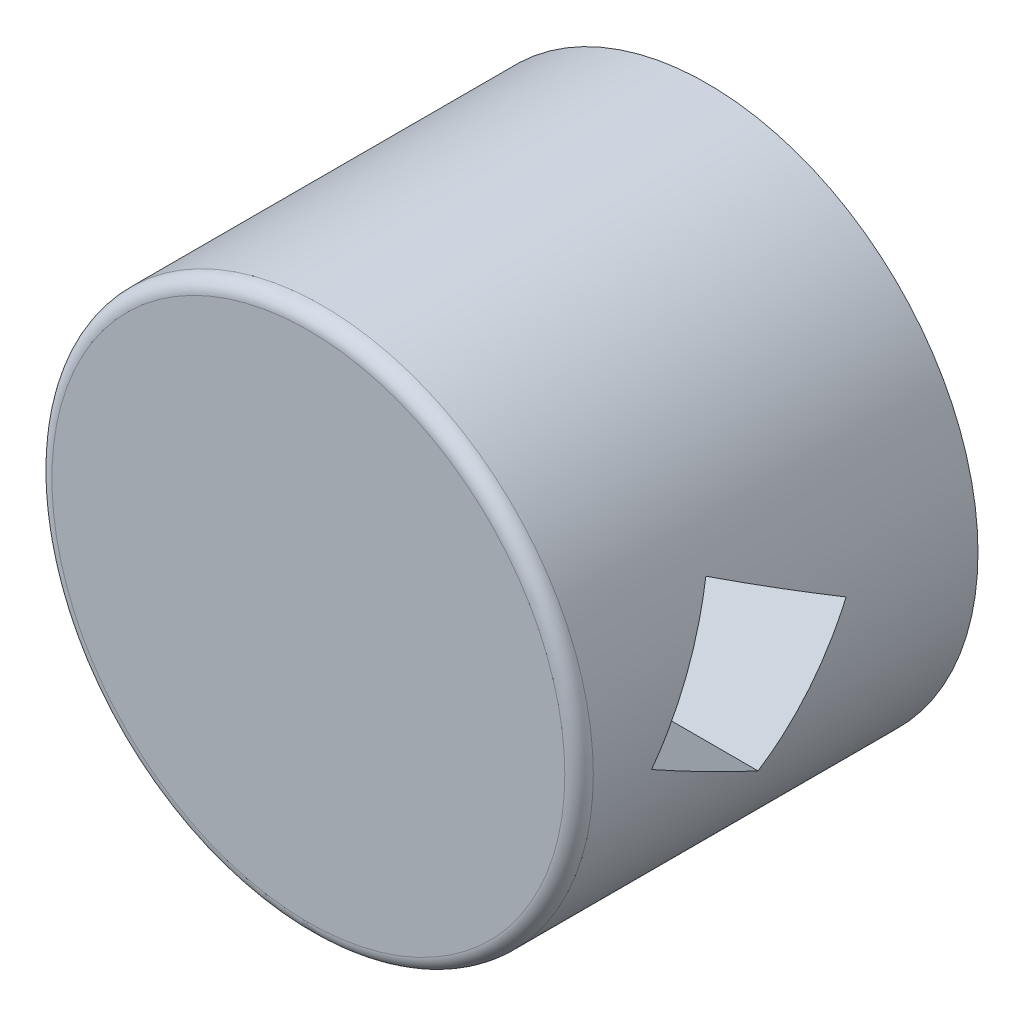
SolidWorks part; units mm, degrees
material "Acciaio al carbonio semplice"
ref_plane "Front Plane" through (0, 0, 0) normal (0, 0, 1) x (1, 0, 0)
ref_plane "Top Plane" through (0, 0, 0) normal (0, 1, 0) x (1, 0, 0)
ref_plane "Right Plane" through (0, 0, 0) normal (1, 0, 0) x (0, 0, -1)
other "Centro di massa"
sketch "Sketch1" plane through (0, 0, 0) normal (0, 0, 1) x (1, 0, 0)
  circle A0 centre (0, 0) radius 95
  dimension "D1" = 190
extrude "Boss-Extrude1" add sketch "Sketch1" along normal mid plane 140
sketch "Sketch2" plane through (0, 0, -70) normal (0, 0, -1) x (-1, 0, 0)
  circle A0 centre (0, 0) radius 80
  dimension "D1" = 160
extrude "Cut-Extrude4" cut sketch "Sketch2" against normal blind 20
sketch "Sketch5" plane through (0, 0, -50) normal (0, 0, -1) x (-1, 0, 0)
  circle A0 centre (0, 0) radius 85
  dimension "D1" = 170
extrude "Cut-Extrude5" cut sketch "Sketch5" against normal blind 10
fillet "Raccordo1" radius 5 1 edges at (95, 0, 70)
ref_axis "Assi2" through (0, 0, 65) along (0, 0, -1)
sketch "Schizzo2" plane through (0, 0, 0) normal (1, 0, 0) x (0, 0, -1)
  line L0 (24.1506, 9.1506) -> (-19.1506, 34.1506)
  line L1 (24.1506, 9.1506) -> (-0.8494, -34.1506)
  line L2 (-19.1506, 34.1506) -> (-44.1506, -9.1506)
  line L3 (-0.8494, -34.1506) -> (-44.1506, -9.1506)
  line L4 (-31.6506, 12.5) -> (11.6506, -12.5) construction
  line L5 (2.5, 21.6506) -> (-22.5, -21.6506) construction
  line L6 (70, -95) -> (70, 95) construction
  line L7 (-65, 0) -> (70, 0) construction
  point P1 (-10, 0)
  dimension "D1" = 50
  dimension "D2" = 50
  dimension "D3" = 80
  dimension "D4" = 30
extrude "Taglio-Estrusione1" cut sketch "Schizzo2" against normal through all both and the other way through all
